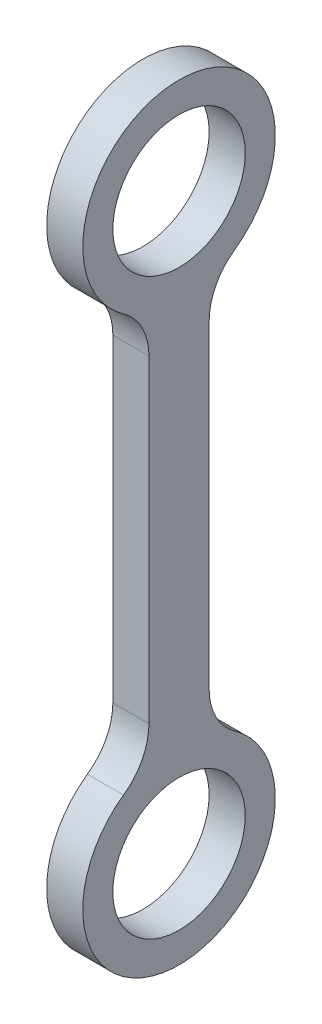
SolidWorks part; units mm, degrees
ref_plane "Front Plane" through (0, 0, 0) normal (0, 0, 1) x (1, 0, 0)
ref_plane "Top Plane" through (0, 0, 0) normal (0, 1, 0) x (1, 0, 0)
ref_plane "Right Plane" through (0, 0, 0) normal (1, 0, 0) x (0, 0, -1)
sketch "Sketch1" plane through (0, 0, 0) normal (1, 0, 0) x (0, 0, -1)
  line L0 (37.2019, 0) -> (-37.2019, 0) construction
  line L1 (0, 95.3974) -> (0, -95.3974) construction
  line L2 (-5, -15.1987) -> (-5, -80.1987)
  line L3 (5, -15.1987) -> (5, -80.1987)
  circle A0 centre (0, 0) radius 11
  arc A1 (5, -15.1987) -> (-5, -15.1987) centre (0, 0) ccw
  circle A2 centre (0, -95.3974) radius 11
  arc A3 (-5, -80.1987) -> (5, -80.1987) centre (0, -95.3974) ccw
  point P4 (0, 0)
  point P8 (0, 0)
  dimension "D1" = 22
  dimension "D2" = 32
  dimension "D3" = 22
  dimension "D4" = 32
  dimension "D5" = 5
  dimension "D6" = 65
extrude "Boss-Extrude1" add sketch "Sketch1" along normal blind 3 and the other way blind 3
fillet "Fillet1" radius 10 4 edges at (0, -80.1987, -5) (0, -80.1987, 5) (0, -15.1987, -5) (0, -15.1987, 5)
